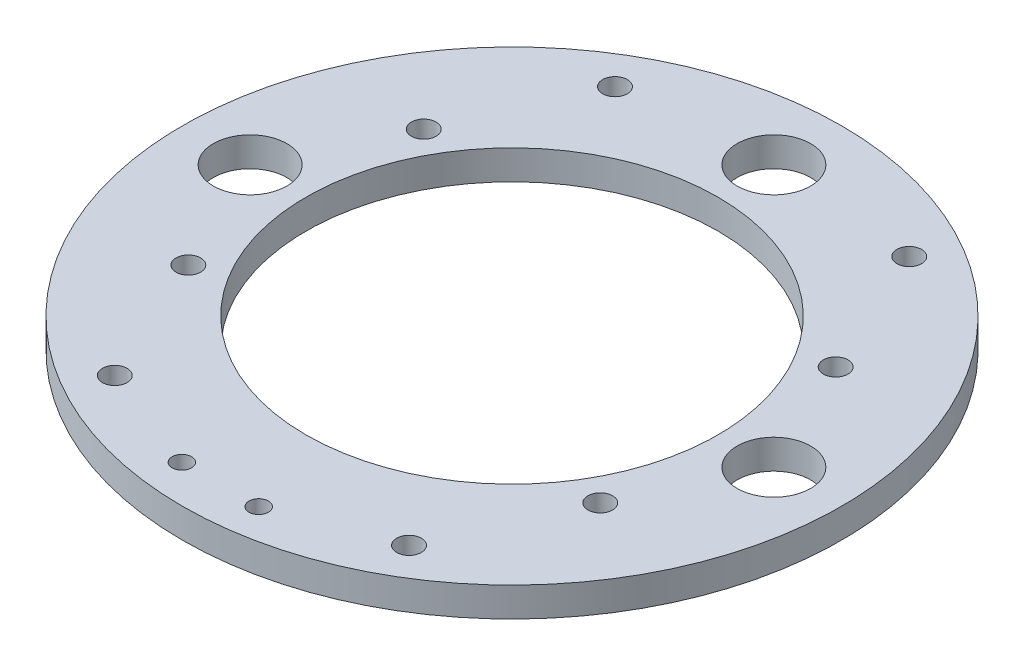
SolidWorks part; units mm, degrees
material "5052-H34"
ref_plane "正面" through (0, 0, 0) normal (0, 0, 1) x (1, 0, 0)
ref_plane "平面" through (0, 0, 0) normal (0, 1, 0) x (1, 0, 0)
ref_plane "右側面" through (0, 0, 0) normal (1, 0, 0) x (0, 0, -1)
sketch "ｽｹｯﾁ1" plane through (0, 0, 0) normal (0, 1, 0) x (1, 0, 0)
  line L0 (0, 42.5) -> (0, 0) construction
  line L1 (-25, 42.5) -> (25, 42.5) construction
  line L2 (-25, 42.5) -> (-25, -42.5) construction
  line L3 (-25, -42.5) -> (25, -42.5) construction
  line L4 (25, 42.5) -> (25, -42.5) construction
  line L5 (-25, 42.5) -> (25, -42.5) construction
  line L6 (-25, -42.5) -> (25, 42.5) construction
  line L7 (0, 0) -> (25, 0) construction
  line L8 (0, 0) -> (0, -50) construction
  line L9 (0, 0) -> (6.5263, -49.5722) construction
  line L11 (-35, 20) -> (35, 20) construction
  line L12 (-35, 20) -> (-35, -20) construction
  line L13 (-35, -20) -> (35, -20) construction
  line L14 (35, 20) -> (35, -20) construction
  line L15 (-35, 20) -> (35, -20) construction
  line L16 (-35, -20) -> (35, 20) construction
  line L17 (30, 50) -> (40, 50) construction
  line L18 (30, 50) -> (30, -50) construction
  line L19 (30, -50) -> (40, -50) construction
  line L20 (40, 50) -> (40, -50) construction
  line L21 (30, 50) -> (40, -50) construction
  line L22 (30, -50) -> (40, 50) construction
  circle A0 centre (0, 0) radius 35
  circle A1 centre (0, 0) radius 56
  circle A2 centre (25, 42.5) radius 2.1
  circle A3 centre (-25, 42.5) radius 2.1
  circle A4 centre (25, -42.5) radius 2.1
  circle A5 centre (-25, -42.5) radius 2.1
  circle A6 centre (0, 0) radius 50 construction
  circle A7 centre (6.5263, -49.5722) radius 1.65
  circle A8 centre (-6.5263, -49.5722) radius 1.65
  circle A9 centre (35, 20) radius 2.1
  circle A10 centre (35, -20) radius 2.1
  circle A11 centre (-35, 20) radius 2.1
  circle A12 centre (-35, -20) radius 2.1
  circle A13 centre (0, 0) radius 44.5 construction
  circle A14 centre (-35, -20) radius 4 construction
  circle A15 centre (25, 42.5) radius 4 construction
  circle A16 centre (0, 44.5) radius 6.25
  circle A17 centre (-44.5, 0) radius 6.25
  circle A18 centre (44.5, 0) radius 6.25
  point P31 (35, 0)
  dimension "D1" = 112
  dimension "D2" = 70
  dimension "D5" = 4.2
  dimension "D6" = 100
  dimension "D7" = 3.3
  dimension "D11" = 4.2
  dimension "D12" = 89
  dimension "D13" = 8
  dimension "D14" = 8
  dimension "D17" = 12.5
  dimension "D3" = 50
  dimension "D4" = 85
  dimension "D8" = 7.5
  dimension "D9" = 40
  dimension "D10" = 70
  dimension "D15" = 10
  dimension "D16" = 100
extrude "ﾎﾞｽ - 押し出し1" add sketch "ｽｹｯﾁ1" along normal blind 5
